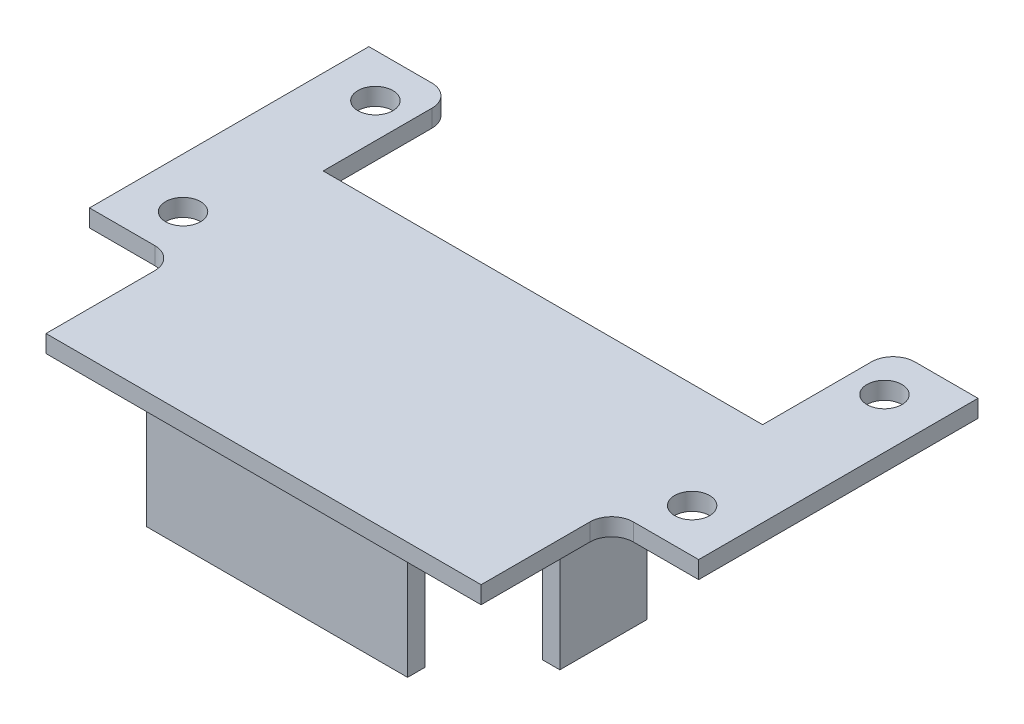
SolidWorks part; units mm, degrees
ref_plane "Front Plane" through (0, 0, 0) normal (0, 0, 1) x (1, 0, 0)
ref_plane "Top Plane" through (0, 0, 0) normal (0, 1, 0) x (1, 0, 0)
ref_plane "Right Plane" through (0, 0, 0) normal (1, 0, 0) x (0, 0, -1)
sketch "Sketch1" plane through (0, 0, 0) normal (0, 1, 0) x (1, 0, 0)
  line L0 (0, 0) -> (0, 10.0958) construction
  line L1 (44.45, -20.3835) -> (-44.45, -20.3835)
  line L2 (44.45, -20.3835) -> (44.45, 20.3835)
  line L3 (44.45, 20.3835) -> (-44.45, 20.3835) construction
  line L4 (-44.45, -20.3835) -> (-44.45, 20.3835)
  line L5 (44.45, -20.3835) -> (-44.45, 20.3835) construction
  line L6 (44.45, 20.3835) -> (-44.45, -20.3835) construction
  line L7 (0, 0) -> (9.14, 0) construction
  line L13 (-32.0675, 17.2085) -> (-32.0675, 1.3335)
  line L14 (-44.45, 20.3835) -> (-35.2425, 20.3835)
  line L15 (-32.0675, 1.3335) -> (32.0675, 1.3335)
  line L16 (32.0675, 17.2085) -> (32.0675, 1.3335)
  line L17 (44.45, 20.3835) -> (35.2425, 20.3835)
  circle A0 centre (37.1475, -14.0335) radius 2.5527
  circle A2 centre (37.1475, 14.0335) radius 2.5527
  circle A3 centre (-37.1475, -14.0335) radius 2.5527
  circle A4 centre (-37.1475, 14.0335) radius 2.5527
  arc A7 (-32.0675, 17.2085) -> (-35.2425, 20.3835) centre (-35.2425, 17.2085) ccw
  arc A8 (32.0675, 17.2085) -> (35.2425, 20.3835) centre (35.2425, 17.2085) cw
  point P0 (0, 0)
  point P19 (0, 1.3335)
  point P22 (0, 14.0335)
  point P23 (-32.0675, 20.3835)
  point P24 (12.7, 14.0335)
  point P27 (-12.7, 14.0335)
  point P30 (32.0675, 20.3835)
  dimension "D3" = 5.1054
  dimension "D6" = 28.067
  dimension "D7" = 5.1054
  dimension "D10" = 5.08
  dimension "D12" = 3.175
  dimension "D1" = 6.35
  dimension "D2" = 88.9
  dimension "D4" = 6.35
  dimension "D5" = 7.3025
  dimension "D8" = 7.3025
  dimension "D9" = 12.7
  dimension "D11" = 19.05
extrude "Boss-Extrude1" add sketch "Sketch1" along normal blind 2.54
sketch "Sketch7" plane through (0, 2.54, 0) normal (0, 1, 0) x (1, 0, 0)
  line L1 (-44.45, -20.3835) -> (44.45, -20.3835)
  line L2 (-44.45, -20.3835) -> (-44.45, -39.4335)
  line L3 (-44.45, -39.4335) -> (44.45, -39.4335)
  line L4 (44.45, -20.3835) -> (44.45, -39.4335)
  point P5 (0, 0)
  dimension "D1" = 19.05
extrude "Boss-Extrude2" add sketch "Sketch7" against normal up to surface (2.54 mm away) up to face at (0, 0, -7.9166)
sketch "Sketch6" plane through (0, 0, 0) normal (0, -1, 0) x (-1, 0, 0)
  line L0 (0, 1.3335) -> (0, -39.4335) construction
  line L5 (-32.0675, 1.3335) -> (32.0675, 1.3335) construction
  line L11 (-44.45, -39.4335) -> (44.45, -39.4335) construction
  line L26 (25.4, -33.655) -> (-25.4, -33.655) construction
  line L27 (25.4, -33.655) -> (25.4, -4.445) construction
  line L28 (25.4, -4.445) -> (-25.4, -4.445) construction
  line L29 (-25.4, -33.655) -> (-25.4, -4.445) construction
  line L30 (25.4, -33.655) -> (-25.4, -4.445) construction
  line L31 (25.4, -4.445) -> (-25.4, -33.655) construction
  line L32 (0, -19.05) -> (44.45, -19.05) construction
  line L33 (44.45, 20.3835) -> (44.45, -39.4335) construction
  line L34 (-19.05, -34.925) -> (-19.05, -37.465)
  line L35 (26.67, -34.925) -> (-26.67, -34.925) construction
  line L36 (26.67, -34.925) -> (26.67, -3.175) construction
  line L37 (26.67, -3.175) -> (-26.67, -3.175) construction
  line L38 (-26.67, -34.925) -> (-26.67, -3.175) construction
  line L39 (26.67, -34.925) -> (-26.67, -3.175) construction
  line L40 (26.67, -3.175) -> (-26.67, -34.925) construction
  line L41 (-19.05, -34.925) -> (19.05, -34.925)
  line L42 (0, -34.925) -> (0, -37.465) construction
  line L43 (-19.05, -37.465) -> (19.05, -37.465)
  line L44 (19.05, -34.925) -> (19.05, -37.465)
  line L45 (-19.05, -3.175) -> (-19.05, -0.635)
  line L46 (-19.05, -3.175) -> (19.05, -3.175)
  line L47 (0, -3.175) -> (0, -0.635) construction
  line L48 (-19.05, -0.635) -> (19.05, -0.635)
  line L49 (19.05, -3.175) -> (19.05, -0.635)
  line L50 (26.67, -25.4) -> (29.21, -25.4)
  line L51 (26.67, -19.05) -> (29.21, -19.05) construction
  line L52 (26.67, -25.4) -> (26.67, -12.7)
  line L53 (26.67, -12.7) -> (29.21, -12.7)
  line L54 (29.21, -25.4) -> (29.21, -12.7)
  line L55 (-26.67, -25.4) -> (-26.67, -12.7)
  line L56 (-26.67, -12.7) -> (-29.21, -12.7)
  line L57 (-29.21, -25.4) -> (-29.21, -12.7)
  line L58 (-26.67, -25.4) -> (-29.21, -25.4)
  point P14 (0, -19.05)
  point P29 (19.05, -1.905)
  point P30 (-19.05, -1.905)
  dimension "D1" = 29.21
  dimension "D2" = 50.8
  dimension "D3" = 1.27
  dimension "D4" = 1.27
  dimension "D5" = 19.05
  dimension "D6" = 2.54
  dimension "D7" = 19.05
  dimension "D8" = 2.54
  dimension "D9" = 2.54
  dimension "D10" = 6.35
extrude "Boss-Extrude3" add sketch "Sketch6" along normal blind 16.51
sketch "Sketch8" plane through (0, 0, 0) normal (0, -1, 0) x (1, 0, 0)
  line L0 (0, 39.4335) -> (0, -1.3335) construction
  line L1 (-44.45, 39.4335) -> (-31.75, 39.4335)
  line L2 (-44.45, 39.4335) -> (-44.45, 20.3835)
  line L3 (-44.45, 20.3835) -> (-34.925, 20.3835)
  line L4 (-31.75, 39.4335) -> (-31.75, 23.5585)
  line L5 (44.45, 39.4335) -> (-44.45, 39.4335) construction
  line L6 (32.0675, -1.3335) -> (-32.0675, -1.3335) construction
  line L7 (44.45, 20.3835) -> (34.925, 20.3835)
  line L8 (31.75, 39.4335) -> (31.75, 23.5585)
  line L9 (44.45, 39.4335) -> (31.75, 39.4335)
  line L10 (44.45, 39.4335) -> (44.45, 20.3835)
  arc A0 (-34.925, 20.3835) -> (-31.75, 23.5585) centre (-34.925, 23.5585) ccw
  arc A1 (34.925, 20.3835) -> (31.75, 23.5585) centre (34.925, 23.5585) cw
  point P13 (-31.75, 20.3835)
  dimension "D3" = 3.175
  dimension "D1" = 12.7
  dimension "D2" = 19.05
extrude "Cut-Extrude1" cut sketch "Sketch8" against normal through all
